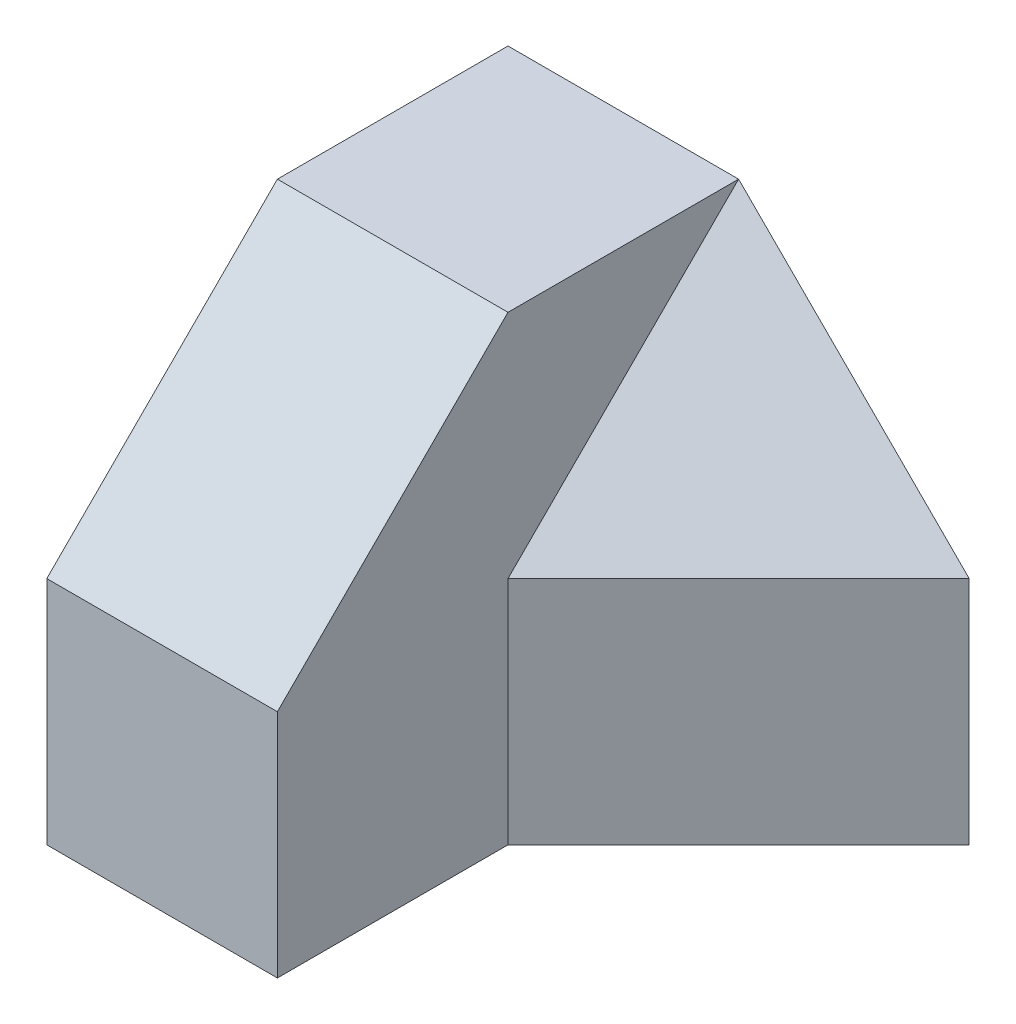
SolidWorks part; units mm, degrees
ref_plane "Front" through (0, 0, 0) normal (0, 0, 1) x (1, 0, 0)
ref_plane "Top" through (0, 0, 0) normal (0, 1, 0) x (1, 0, 0)
ref_plane "Right" through (0, 0, 0) normal (1, 0, 0) x (0, 0, -1)
sketch "Sketch2" plane through (0, 0, 0) normal (1, 0, 0) x (0, 0, -1)
  line L1 (-2, -2) -> (2, -2)
  line L2 (-2, -2) -> (-2, 2)
  line L3 (-2, 2) -> (2, 2)
  line L4 (2, -2) -> (2, 2)
  line L5 (-2, -2) -> (2, 2) construction
  line L6 (-2, 2) -> (2, -2) construction
  point P0 (0, 0)
  dimension "D1" = 4
  dimension "D2" = 4
extrude "Boss-Extrude1" add sketch "Sketch2" along normal blind 4
sketch "Sketch3" plane through (0, 0, 2) normal (0, 0, 1) x (1, 0, 0)
  line L0 (2, 2) -> (4, 0)
  line L1 (4, 2) -> (0, 2) construction
  line L2 (4, 2) -> (4, -2) construction
  line L3 (4, 0) -> (4, 2)
  line L4 (4, 2) -> (2, 2)
extrude "Cut-Extrude1" cut sketch "Sketch3" against normal blind 4
sketch "Sketch4" plane through (0, 2, 0) normal (0, 1, 0) x (1, 0, 0)
  line L2 (2, 2) -> (2, -2) construction
  line L3 (2, 0) -> (4, 2)
  line L4 (4, 2) -> (4, -2)
  line L6 (2, 0) -> (2, -2)
  line L7 (4, -2) -> (2, -2)
extrude "Cut-Extrude2" cut sketch "Sketch4" against normal blind 4
fillet "Chamfer1" radius 2 1 edges at (1, 2, 2) profile chamfer
sketch3d "3DSketch1"
  line L1 (2, -2, 0) -> (2, 2, 0) construction
  line L2 (2, 0, 0) -> (4, 0, -2)
  line L3 (4, 0, -2) -> (2, 2, -2)
  line L5 (2, 2, -2) -> (2, 0, 0)
  point P9 (1.9353, 2, -2)
extrude "Cut-Extrude4" cut sketch "3DSketch1" along direction (0, -1, 0) on the side of the normal blind 4
